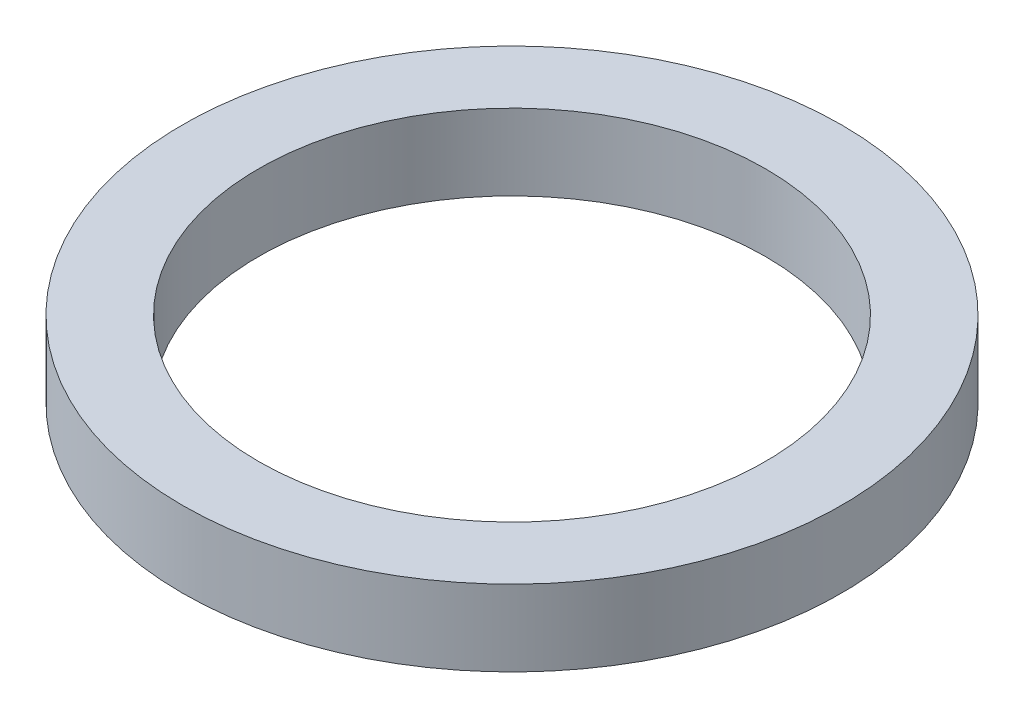
SolidWorks part; units mm, degrees
ref_plane "Front Plane" through (0, 0, 0) normal (0, 0, 1) x (1, 0, 0)
ref_plane "Top Plane" through (0, 0, 0) normal (0, 1, 0) x (1, 0, 0)
ref_plane "Right Plane" through (0, 0, 0) normal (1, 0, 0) x (0, 0, -1)
sketch "Sketch1" plane through (0, 0, 0) normal (0, 1, 0) x (1, 0, 0)
  circle A0 centre (0, 0) radius 65
  dimension "FLANGE_OD" = 130
extrude "Boss-Extrude1" add sketch "Sketch1" along normal blind 15
sketch "Sketch2" plane through (0, 0, 0) normal (0, 1, 0) x (1, 0, 0)
  circle A0 centre (0, 0) radius 50
  dimension "BORE_D" = 100
extrude "Cut-Extrude1" cut sketch "Sketch2" along normal through all
sketch "Sketch3" plane through (0, 15, 0) normal (0, 1, 0) x (1, 0, 0)
  circle A0 centre (0, 0) radius 30.5477 construction
  circle A1 centre (-30.5477, 0) radius 1.7595
  dimension "BOLT_D" = 3.519
  dimension "BOLT_PCD" = 61.0955
extrude "Cut-Extrude2" cut sketch "Sketch3" against normal blind 10.4542 rebuild error yes
pattern_circular "CirPattern1" count 4 over 360 rebuild error yes
